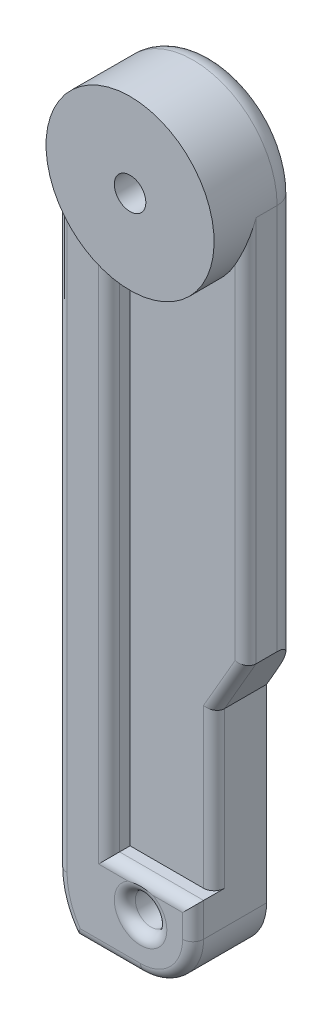
SolidWorks part; units mm, degrees
ref_plane "Front Plane" through (0, 0, 0) normal (0, 0, 1) x (1, 0, 0)
ref_plane "Top Plane" through (0, 0, 0) normal (0, 1, 0) x (1, 0, 0)
ref_plane "Right Plane" through (0, 0, 0) normal (1, 0, 0) x (0, 0, -1)
sketch "Sketch1" plane through (0, 0, 0) normal (0, 0, 1) x (1, 0, 0)
  line L0 (0, 0) -> (0, 60) construction
  line L1 (-8, 0) -> (-8, 60)
  line L2 (8, 23.2147) -> (8, 60)
  line L3 (5, 0) -> (5, 18.0185)
  line L4 (5, 18.0185) -> (8, 23.2147)
  line L5 (0, -5) -> (-6.245, -5)
  arc A0 (-8, 0) -> (-6.245, -5) centre (0, 0) ccw
  arc A1 (8, 60) -> (-8, 60) centre (0, 60) ccw
  circle A2 centre (0, 60) radius 1.5
  circle A3 centre (0, 0) radius 1.5
  arc A4 (0, -5) -> (5, 0) centre (0, 0) ccw
  point P3 (0, 30)
  dimension "D1" = 3
  dimension "D3" = 8
  dimension "D4" = 5
  dimension "D2" = 60
  dimension "D5" = 30
extrude "Boss-Extrude1" add sketch "Sketch1" along normal blind 5
sketch "Sketch2" plane through (0, 0, 5) normal (0, 0, 1) x (1, 0, 0)
  circle A0 centre (0, 60) radius 8
  circle A1 centre (0, 60) radius 1.5
extrude "Boss-Extrude2" add sketch "Sketch2" along normal blind 3
sketch "Sketch3" plane through (0, 0, 5) normal (0, 0, 1) x (1, 0, 0)
  line L1 (-8, 0) -> (-8, 60)
  line L2 (-8, 60) -> (-3, 55.3716)
  line L3 (-3, 55.3716) -> (-3, 3.2035)
  line L5 (-3, -5) -> (-6.245, -5)
  line L6 (-3, 3.2035) -> (5, 3.2035)
  line L7 (5, 0) -> (5, 18.0185) construction
  line L8 (5, 3.2035) -> (5, 0)
  line L9 (0, -5) -> (-3, -5)
  arc A5 (-6.245, -5) -> (-8, 0) centre (0, 0) cw
  arc A6 (5, 0) -> (0, -5) centre (0, 0) cw
  circle A7 centre (0, 0) radius 1.5
  dimension "D1" = 5
extrude "Boss-Extrude3" add sketch "Sketch3" along normal blind 2
fillet "Fillet1" radius 2 4 edges at (8, 41.6073, 0) (-8, 30, 0) (-7.5485, -2.6495, 0) (0, 68, 0)
sketch "Sketch4" plane through (0, 0, 0) normal (0, 0, -1) x (-1, 0, 0)
  line L1 (3.1754, 60) -> (1.5877, 62.75)
  line L2 (1.5877, 62.75) -> (-1.5877, 62.75)
  line L3 (-1.5877, 62.75) -> (-3.1754, 60)
  line L4 (-3.1754, 60) -> (-1.5877, 57.25)
  line L5 (-1.5877, 57.25) -> (1.5877, 57.25)
  line L6 (1.5877, 57.25) -> (3.1754, 60)
  line L7 (3.1754, 0) -> (1.5877, 2.75)
  line L8 (1.5877, 2.75) -> (-1.5877, 2.75)
  line L9 (-1.5877, 2.75) -> (-3.1754, 0)
  line L10 (-3.1754, 0) -> (-1.5877, -2.75)
  line L11 (-1.5877, -2.75) -> (1.5877, -2.75)
  line L12 (1.5877, -2.75) -> (3.1754, 0)
  circle A0 centre (0, 60) radius 2.75 construction
  circle A1 centre (0, 0) radius 2.75 construction
  dimension "D1" = 5.5
extrude "Cut-Extrude1" cut sketch "Sketch4" against normal blind 2.5
fillet "Fillet2" radius 1 10 edges at (-3, 52.5838, 6) (-3.1225, -5, 7) (-7.5485, -2.6495, 7) (-8, 30, 7) (-6.6332, 55.5279, 7) (-3, 27.8936, 7) (1, 3.2035, 7) (5, 1.6017, 7) (3.5355, -3.5355, 7) (1.5, 0, 7)
fillet "Fillet3" radius 1 3 edges at (8, 41.6073, 5) (6.5, 20.6166, 5) (5, 10.611, 5)
